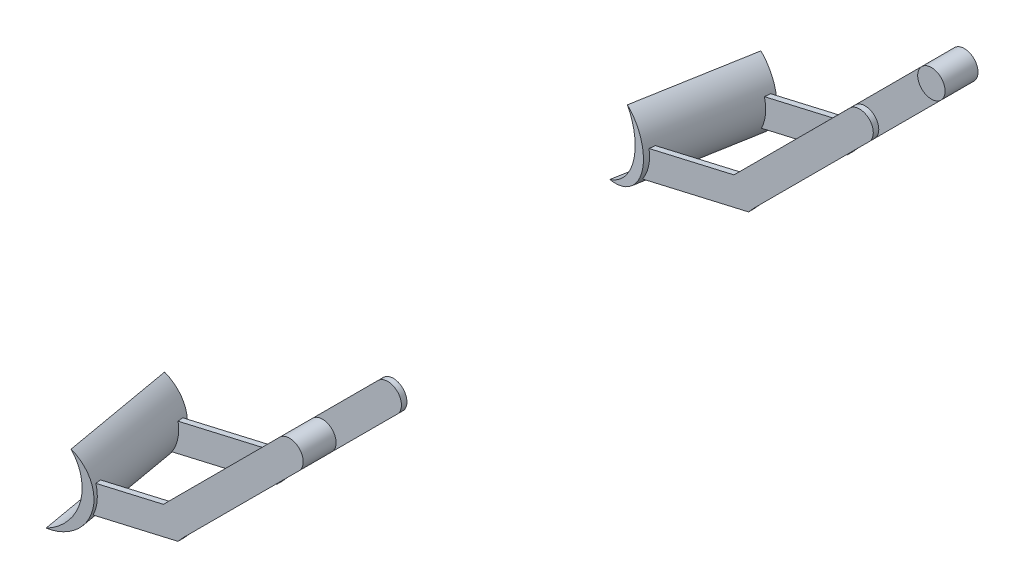
SolidWorks part; units mm, degrees
ref_plane "Front Plane" through (0, 0, 0) normal (0, 0, 1) x (1, 0, 0)
ref_plane "Top Plane" through (0, 0, 0) normal (0, 1, 0) x (1, 0, 0)
ref_plane "Right Plane" through (0, 0, 0) normal (1, 0, 0) x (0, 0, -1)
sketch "Sketch2" plane through (0, 0, 0) normal (0, 0, 1) x (1, 0, 0)
  line L1 (-17.6777, 17.6777) -> (-229.8097, -194.4544)
  line L2 (-229.8097, -194.4544) -> (-364.7177, -225.6003)
  line L3 (17.6777, -17.6777) -> (-192.6525, -227.9109)
  line L7 (-218.5622, -243.1729) -> (-364.7177, -276.9155)
  line L8 (-192.6525, -227.9109) -> (-203.2013, -239.6265)
  line L9 (-218.5622, -243.1729) -> (-203.2013, -239.6265)
  line L10 (-364.7177, -276.9155) -> (-364.7177, -225.6003)
  line L11 (-229.8097, -194.4544) -> (-375.9652, -228.197) construction
  arc A0 (17.6777, -17.6777) -> (-17.6777, 17.6777) centre (0, 0) ccw
  dimension "D1" = 50
  dimension "D2" = 300
  dimension "D3" = 150
  dimension "D4" = 148
  dimension "D5" = 50
extrude "Boss-Extrude1" add sketch "Sketch2" along normal blind 10
sketch "Sketch4" plane through (0, 0, 0) normal (0, 0, -1) x (-1, 0, 0)
  circle A0 centre (0, 0) radius 25
extrude "Boss-Extrude2" add sketch "Sketch4" along normal blind 50
sketch "Sketch6" plane through (0, 0, 10) normal (0, 0, 1) x (1, 0, 0)
  line L0 (-364.7177, -225.6003) -> (-364.7177, -276.9155) construction
ref_plane "Plane1" through (-9.2875, 0, -52.6719) normal (0.1736, 0, 0.9848) x (0, -1, 0)
sketch "Sketch8" plane through (-9.2875, 0, -52.6719) normal (0.1736, 0, 0.9848) x (0, -1, 0)
  arc A2 (177.731, -382.6204) -> (318.5477, -422.148) centre (232.1578, -459.3183) cw
  arc A4 (177.731, -382.6204) -> (318.5477, -422.148) centre (242.4224, -422.7506) cw
extrude "Boss-Extrude3" add sketch "Sketch8" along normal blind 10 and the other way blind 200
ref_plane "Plane2" through (0, 0, -170) normal (0, 0, -1) x (-1, 0, 0)
sketch "Sketch9" plane through (0, 0, -170) normal (0, 0, -1) x (-1, 0, 0)
  line L6 (395.4526, -284.0112) -> (395.4526, -232.696)
  line L8 (192.6525, -227.9109) -> (203.2013, -239.6265)
  line L9 (203.2013, -239.6265) -> (395.4526, -284.0112)
  line L10 (-17.6777, -17.6777) -> (192.6525, -227.9109)
  line L11 (229.8097, -194.4544) -> (395.4526, -232.696)
  line L12 (19.4796, 15.7789) -> (229.8097, -194.4544)
  arc A1 (-17.6777, -17.6777) -> (19.4796, 15.7789) centre (0.901, -0.9494) cw
  dimension "D2" = 170
extrude "Boss-Extrude4" add sketch "Sketch9" along normal blind 10
ref_plane "Plane3" through (0, 0, -605) normal (0, 0, -1) x (-1, 0, 0)
mirror "Mirror6" about plane through (0, 0, -605) normal (0, 0, -1) of bodies 108
